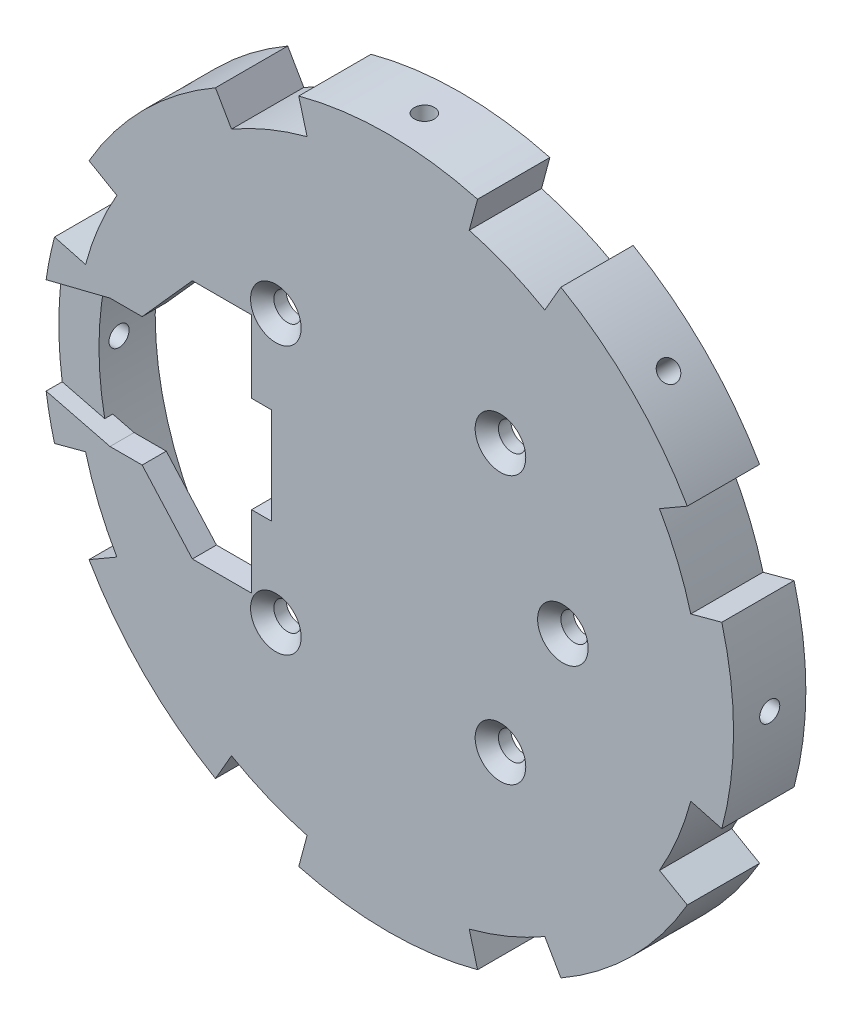
SolidWorks part; units mm, degrees
ref_plane "前视基准面" through (0, 0, 0) normal (0, 0, 1) x (1, 0, 0)
ref_plane "上视基准面" through (0, 0, 0) normal (0, 1, 0) x (1, 0, 0)
ref_plane "右视基准面" through (0, 0, 0) normal (1, 0, 0) x (0, 0, -1)
sketch "草图1" plane through (0, 0, 0) normal (0, 0, 1) x (1, 0, 0)
  line L16 (21.5, 37.2391) -> (19.5, 33.775)
  line L17 (11.1292, 41.5348) -> (10.0939, 37.6711)
  line L18 (-11.1292, 41.5348) -> (-10.0939, 37.6711)
  line L19 (37.2391, 21.5) -> (33.775, 19.5)
  line L20 (41.5348, 11.1292) -> (37.6711, 10.0939)
  line L21 (41.5348, -11.1292) -> (37.6711, -10.0939)
  line L22 (37.2391, -21.5) -> (33.775, -19.5)
  line L23 (21.5, -37.2391) -> (19.5, -33.775)
  line L24 (11.1292, -41.5348) -> (10.0939, -37.6711)
  line L25 (-11.1292, -41.5348) -> (-10.0939, -37.6711)
  line L26 (-21.5, -37.2391) -> (-19.5, -33.775)
  line L27 (-37.2391, -21.5) -> (-33.775, -19.5)
  line L28 (-41.5348, -11.1292) -> (-37.6711, -10.0939)
  line L29 (-41.5348, 11.1292) -> (-37.6711, 10.0939)
  line L30 (-37.2391, 21.5) -> (-33.775, 19.5)
  line L31 (-21.5, 37.2391) -> (-19.5, 33.775)
  circle A1 centre (0, 0) radius 38
  arc A6 (0, 43) -> (-11.1292, 41.5348) centre (0, 0) ccw
  arc A31 (0, 43) -> (11.1292, 41.5348) centre (0, 0) cw
  arc A32 (10.0939, 37.6711) -> (19.5, 33.775) centre (0, 0) cw
  arc A33 (30.4056, 30.4056) -> (21.5, 37.2391) centre (0, 0) ccw
  arc A34 (30.4056, 30.4056) -> (37.2391, 21.5) centre (0, 0) cw
  arc A35 (33.775, 19.5) -> (37.6711, 10.0939) centre (0, 0) cw
  arc A36 (43, 0) -> (41.5348, 11.1292) centre (0, 0) ccw
  arc A37 (43, 0) -> (41.5348, -11.1292) centre (0, 0) cw
  arc A38 (37.6711, -10.0939) -> (33.775, -19.5) centre (0, 0) cw
  arc A39 (30.4056, -30.4056) -> (37.2391, -21.5) centre (0, 0) ccw
  arc A40 (30.4056, -30.4056) -> (21.5, -37.2391) centre (0, 0) cw
  arc A41 (19.5, -33.775) -> (10.0939, -37.6711) centre (0, 0) cw
  arc A42 (0, -43) -> (11.1292, -41.5348) centre (0, 0) ccw
  arc A43 (0, -43) -> (-11.1292, -41.5348) centre (0, 0) cw
  arc A44 (-10.0939, -37.6711) -> (-19.5, -33.775) centre (0, 0) cw
  arc A45 (-30.4056, -30.4056) -> (-21.5, -37.2391) centre (0, 0) ccw
  arc A46 (-30.4056, -30.4056) -> (-37.2391, -21.5) centre (0, 0) cw
  arc A47 (-33.775, -19.5) -> (-37.6711, -10.0939) centre (0, 0) cw
  arc A48 (-43, 0) -> (-41.5348, -11.1292) centre (0, 0) ccw
  arc A49 (-43, 0) -> (-41.5348, 11.1292) centre (0, 0) cw
  arc A50 (-37.6711, 10.0939) -> (-33.775, 19.5) centre (0, 0) cw
  arc A51 (-30.4056, 30.4056) -> (-37.2391, 21.5) centre (0, 0) ccw
  arc A52 (-30.4056, 30.4056) -> (-21.5, 37.2391) centre (0, 0) cw
  arc A53 (-19.5, 33.775) -> (-10.0939, 37.6711) centre (0, 0) cw
  point P55 (0, 0)
  point P56 (0, 0)
  dimension "D1" = 8
extrude "凸台-拉伸1" add sketch "草图1" against normal blind 6
sketch "草图2" plane through (0, 0, 0) normal (0, 0, 1) x (1, 0, 0)
  line L16 (-11.1292, 41.5348) -> (-10.0939, 37.6711)
  line L17 (10.0939, 37.6711) -> (11.1292, 41.5348)
  line L18 (21.5, 37.2391) -> (19.5, 33.775)
  line L19 (33.775, 19.5) -> (37.2391, 21.5)
  line L20 (41.5348, 11.1292) -> (37.6711, 10.0939)
  line L21 (37.6711, -10.0939) -> (41.5348, -11.1292)
  line L22 (37.2391, -21.5) -> (33.775, -19.5)
  line L23 (19.5, -33.775) -> (21.5, -37.2391)
  line L24 (11.1292, -41.5348) -> (10.0939, -37.6711)
  line L25 (-10.0939, -37.6711) -> (-11.1292, -41.5348)
  line L26 (-21.5, -37.2391) -> (-19.5, -33.775)
  line L27 (-33.775, -19.5) -> (-37.2391, -21.5)
  line L28 (-41.5348, -11.1292) -> (-37.6711, -10.0939)
  line L29 (-37.6711, 10.0939) -> (-41.5348, 11.1292)
  line L30 (-37.2391, 21.5) -> (-33.775, 19.5)
  line L31 (-19.5, 33.775) -> (-21.5, 37.2391)
  arc A27 (0, 43) -> (11.1292, 41.5348) centre (0, 0) cw
  arc A28 (10.0939, 37.6711) -> (19.5, 33.775) centre (0, 0) cw
  arc A29 (0, 43) -> (-11.1292, 41.5348) centre (0, 0) ccw
  arc A30 (30.4056, 30.4056) -> (21.5, 37.2391) centre (0, 0) ccw
  arc A31 (30.4056, 30.4056) -> (37.2391, 21.5) centre (0, 0) cw
  arc A32 (33.775, 19.5) -> (37.6711, 10.0939) centre (0, 0) cw
  arc A33 (43, 0) -> (41.5348, 11.1292) centre (0, 0) ccw
  arc A34 (43, 0) -> (41.5348, -11.1292) centre (0, 0) cw
  arc A35 (37.6711, -10.0939) -> (33.775, -19.5) centre (0, 0) cw
  arc A36 (30.4056, -30.4056) -> (37.2391, -21.5) centre (0, 0) ccw
  arc A37 (30.4056, -30.4056) -> (21.5, -37.2391) centre (0, 0) cw
  arc A38 (19.5, -33.775) -> (10.0939, -37.6711) centre (0, 0) cw
  arc A39 (0, -43) -> (11.1292, -41.5348) centre (0, 0) ccw
  arc A40 (0, -43) -> (-11.1292, -41.5348) centre (0, 0) cw
  arc A41 (-10.0939, -37.6711) -> (-19.5, -33.775) centre (0, 0) cw
  arc A42 (-30.4056, -30.4056) -> (-21.5, -37.2391) centre (0, 0) ccw
  arc A43 (-30.4056, -30.4056) -> (-37.2391, -21.5) centre (0, 0) cw
  arc A44 (-33.775, -19.5) -> (-37.6711, -10.0939) centre (0, 0) cw
  arc A45 (-43, 0) -> (-41.5348, -11.1292) centre (0, 0) ccw
  arc A46 (-43, 0) -> (-41.5348, 11.1292) centre (0, 0) cw
  arc A47 (-37.6711, 10.0939) -> (-33.775, 19.5) centre (0, 0) cw
  arc A48 (-30.4056, 30.4056) -> (-37.2391, 21.5) centre (0, 0) ccw
  arc A49 (-30.4056, 30.4056) -> (-21.5, 37.2391) centre (0, 0) cw
  arc A50 (-19.5, 33.775) -> (-10.0939, 37.6711) centre (0, 0) cw
  point P43 (0, 0)
extrude "凸台-拉伸2" add sketch "草图2" along normal blind 3
hole_wizard "M3 锥坑平头的锥孔1" positions "3D草图2" profile "草图4" countersink size "M3" standard "BSI" end condition through all
sketch3d "3D草图2"
  point P25 (13.9806, -16.6615, 3)
  point P27 (21.75, 0, 3)
  point P40 (13.9806, 16.6615, 3)
  point P41 (-13.9806, -16.6615, 3)
  point P42 (-21.75, 0, 3)
  point P43 (-13.9806, 16.6615, 3)
sketch "草图4" plane through (13.9806, -16.6615, 3) normal (1, 0, 0) x (0, -1, 0)
  line L0 (0, 0) -> (0, 9)
  line L1 (0, 9) -> (1.7, 9)
  line L2 (1.7, 9) -> (1.7, 1.45)
  line L3 (1.7, 1.45) -> (3.15, 0)
  line L5 (3.15, 0) -> (0, 0)
  line L6 (-1.7, 1.45) -> (-3.15, 0) construction
  line L11 (0, -6.35) -> (0, 107.95) construction
  dimension "通孔孔直径" = 3.4
  dimension "通孔孔深度" = 9
  dimension "近端锥形沉头孔直径" = 6.3
  dimension "近端锥形沉头孔角度" = 90
hole_wizard "M3x0.5 螺纹孔1" positions "3D草图3" profile "草图5" tap size "M3x0.5" standard "BSI" end condition up to next
sketch3d "3D草图3"
  point P5 (0, -43, -1.5)
  point P13 (30.4056, -30.4056, -1.5)
  point P33 (30.4056, 30.4056, -1.5)
  point P43 (43, 0, -1.5)
  point P53 (-30.4056, 30.4056, -1.5)
  point P55 (-30.4056, -30.4056, -1.5)
  point P57 (43, 0, -1.5)
  point P72 (-43, 0, -1.5)
  point P77 (0, 43, -1.5)
sketch "草图5" plane through (0, -43, -1.5) normal (1, 0, 0) x (0, 0, -1)
  line L0 (0, 0) -> (0, 5)
  line L1 (0, 5) -> (1.25, 5)
  line L2 (1.25, 5) -> (1.25, 0)
  line L5 (1.25, 0) -> (0, 0)
  line L11 (0, -6.35) -> (0, 107.95) construction
  dimension "通孔螺纹孔钻头直径" = 2.5
  dimension "通孔螺纹孔钻头深度" = 5
cosmetic thread "孔螺蚊线1" parameters "D2"=3
cosmetic thread "孔螺蚊线2" parameters "D2"=3
cosmetic thread "孔螺蚊线3" parameters "D2"=3
cosmetic thread "孔螺蚊线4" parameters "D2"=3
cosmetic thread "孔螺蚊线5" parameters "D2"=3
cosmetic thread "孔螺蚊线6" parameters "D2"=3
sketch "草图6" plane through (0, 0, 0) normal (0, 0, 1) x (1, 0, 0)
  line L3 (-14.5, -6) -> (-14.5, 6)
  line L4 (-14.5, 6) -> (-17, 6)
  line L13 (-14.5, -6) -> (-17, -6)
  line L21 (-17, -15) -> (-17, -6)
  line L22 (-42.5793, 6) -> (-34.6246, 8)
  line L23 (-42.5793, -6) -> (-34.6246, -8)
  line L24 (-17, 6) -> (-17, 15)
  line L25 (-34.6246, 8) -> (-30.6246, 8)
  line L26 (-17, 15) -> (-24.3746, 15)
  line L27 (-30.6246, 8) -> (-24.3746, 15)
  line L28 (-34.6246, -8) -> (-30.6246, -8)
  line L29 (-30.6246, -8) -> (-24.3746, -15)
  line L30 (-24.3746, -15) -> (-17, -15)
  arc A2 (-41.5348, 11.1292) -> (-41.5348, -11.1292) centre (0, 0) ccw construction
  arc A3 (-42.5793, 6) -> (-42.5793, -6) centre (0, 0) ccw
extrude "切除-拉伸1" cut sketch "草图6" along normal blind 3
sketch "草图9" plane through (0, 0, 0) normal (0, 0, 1) x (1, 0, 0)
  line L0 (-34.6246, 8) -> (-42.5793, 6) construction
  line L1 (-37.2862, 7.3308) -> (-42.5793, 6) construction
  line L2 (-42.5793, 6) -> (-37.2862, 7.3308)
  line L3 (-42.5793, -6) -> (-37.2862, -7.3308)
  arc A0 (-37.2862, -7.3308) -> (-37.2862, 7.3308) centre (0, 0) cw
  arc A1 (-42.5793, -6) -> (-42.5793, 6) centre (0, 0) cw
extrude "凸台-拉伸3" add sketch "草图9" along normal blind 1
